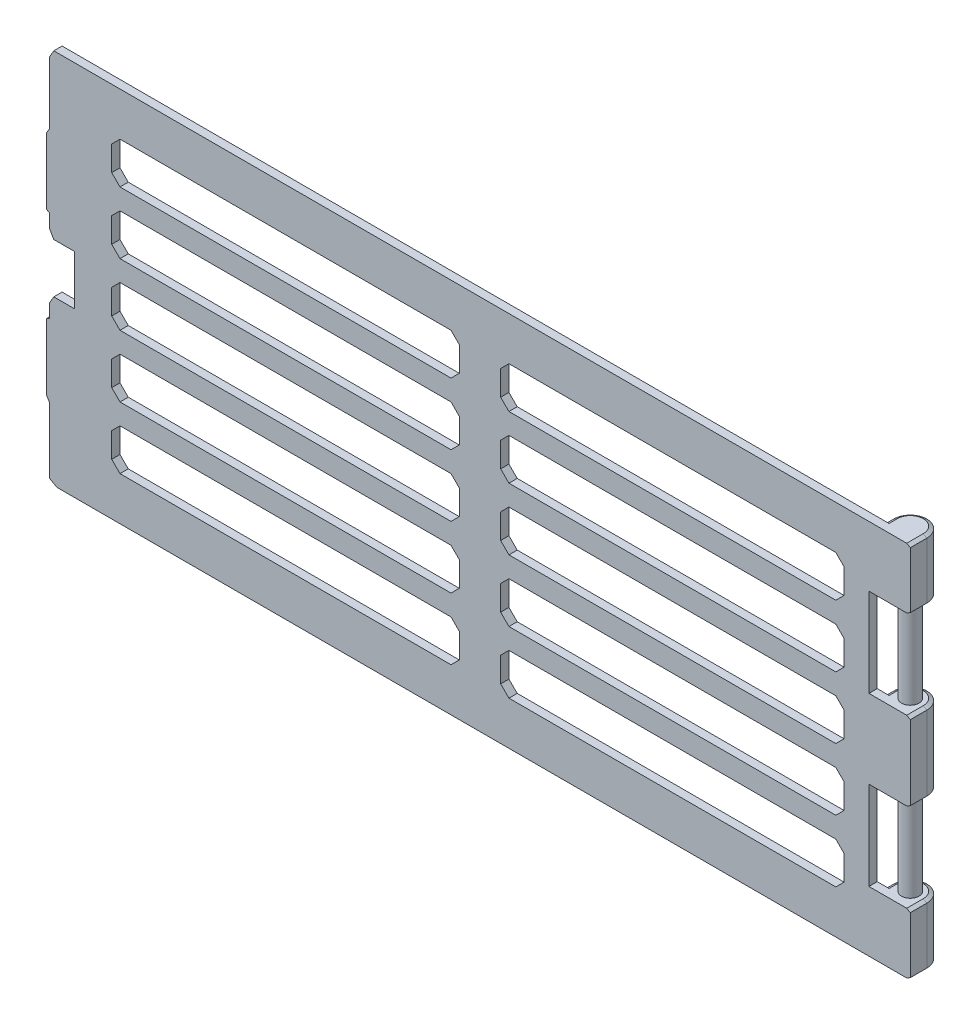
SolidWorks part; units mm, degrees
ref_plane "前视基准面" through (0, 0, 0) normal (0, 0, 1) x (1, 0, 0)
ref_plane "上视基准面" through (0, 0, 0) normal (0, 1, 0) x (1, 0, 0)
ref_plane "右视基准面" through (0, 0, 0) normal (1, 0, 0) x (0, 0, -1)
other "Configuration Table"
sketch "草图1" plane through (0, 0, 0) normal (0, 0, 1) x (1, 0, 0)
  line L1 (-104, 45.5) -> (104, 45.5)
  line L2 (-104, 45.5) -> (-104, -45.5)
  line L3 (-104, -45.5) -> (104, -45.5)
  line L4 (104, 45.5) -> (104, -45.5)
  line L5 (0, -45.5) -> (0, 45.5) construction
  line L6 (-104, 0) -> (104, 0) construction
  point P0 (0, 0)
  dimension "D1" = 91
  dimension "D2" = 208
extrude "凸台-拉伸1" add sketch "草图1" along normal blind 2
sketch "草图3" plane through (0, 45.5, 0) normal (0, 1, 0) x (1, 0, 0)
  line L1 (96, -2) -> (104, -2)
  line L2 (96, -2) -> (96, 6)
  line L3 (96, 6) -> (104, 6)
  line L4 (104, -2) -> (104, 6)
  line L5 (100, 6) -> (100, -2) construction
  line L6 (96, 2) -> (104, 2) construction
  line L7 (104, -2) -> (104, 0) construction
  line L8 (104, -2) -> (-104, -2) construction
  point P0 (100, 2)
  dimension "D1" = 8
  dimension "D2" = 8
extrude "凸台-拉伸2" add sketch "草图3" along direction (0, 1, 0) on the side against the normal up to surface (91 mm away) up to face at (0, -45.5, 1)
sketch "草图2" plane through (0, 0, 2) normal (0, 0, 1) x (1, 0, 0)
  line L0 (104, 30.9) -> (94, 30.9)
  line L1 (104, -45.5) -> (104, 45.5) construction
  line L2 (94, 30.9) -> (94, 45.5)
  line L3 (104, 45.5) -> (-104, 45.5) construction
  line L4 (104, -30.9) -> (94, -30.9)
  line L5 (94, -30.9) -> (94, -45.5)
  line L6 (-104, -45.5) -> (104, -45.5) construction
  line L7 (104, 9.5) -> (94, 9.5)
  line L8 (94, 9.5) -> (94, -9.5)
  line L9 (94, -9.5) -> (104, -9.5)
  line L10 (104, 9.5) -> (104, -9.5)
  line L11 (104, -30.9) -> (104, -45.5)
  line L12 (104, -45.5) -> (94, -45.5)
  line L13 (104, 30.9) -> (104, 45.5)
  line L14 (104, 45.5) -> (94, 45.5)
  line L15 (94, 30.9) -> (94, 9.5)
  line L16 (104, 30.9) -> (104, 9.5)
  line L17 (104, -9.5) -> (104, -30.9)
  line L18 (94, -9.5) -> (94, -30.9)
  point P14 (104, 0)
  dimension "D1" = 9.5
  dimension "D2" = 19
  dimension "D3" = 21.4
  dimension "D4" = 21.4
  dimension "D5" = 10
extrude "切除-拉伸1" cut sketch "草图2" against normal mid plane 46
sketch "草图4" plane through (0, 45.5, 0) normal (0, 1, 0) x (1, 0, 0)
  line L0 (104, 6) -> (96, -2) construction
  line L1 (104, -2) -> (-104, -2) construction
  line L2 (96, 6) -> (96, 0) construction
  circle A0 centre (100, 2) radius 2.1
  dimension "D1" = 4.2
extrude "凸台-拉伸3" add sketch "草图4" against normal up to surface (91 mm away) up to face at (32, -45.5, -1.3333)
fillet "圆角1" radius 4 6 edges at (96, 38.2, -6) (96, 0, -6) (96, -38.2, -6) (104, -38.2, -6) (104, 0, -6) (104, 38.2, -6)
sketch "草图6" plane through (0, 0, 2) normal (0, 0, 1) x (1, 0, 0)
  line L0 (88, -45.5) -> (88, 45.5)
  line L1 (-104, -45.5) -> (104, -45.5) construction
  line L2 (104, 45.5) -> (-104, 45.5) construction
  line L3 (104, 30.9) -> (104, 45.5) construction
  line L4 (-89, -45.5) -> (-89, 45.5)
  line L5 (-104, 45.5) -> (-104, -45.5) construction
  line L6 (-89, 0) -> (88, 0)
  line L7 (88, 15) -> (-89, 15)
  line L8 (88, 30) -> (-89, 30)
  dimension "D1" = 16
  dimension "D2" = 15
  dimension "D3" = 15
  dimension "D4" = 15
extrude "切除-拉伸-薄壁1" cut sketch "草图6" against normal through all thin contours L8 | L7 | L6 thin type mid plane wall 10
mirror "镜向1" about plane through (0, 0, 0) normal (0, 1, 0) of "切除-拉伸-薄壁1"
sketch "草图7" plane through (0, 0, 2) normal (0, 0, 1) x (1, 0, 0)
  line L0 (104, 45.5) -> (-104, 45.5) construction
  line L1 (-5, -45.5) -> (5, -45.5)
  line L2 (-5, -45.5) -> (-5, 45.5)
  line L3 (-5, 45.5) -> (5, 45.5)
  line L4 (5, -45.5) -> (5, 45.5)
  line L5 (0, 45.5) -> (0, -45.5) construction
  line L6 (-5, 0) -> (5, 0) construction
  point P0 (0, 0)
  dimension "D1" = 10
extrude "凸台-拉伸4" add sketch "草图7" against normal up to surface (2 mm away) up to face at (-0.5, -15, 0)
chamfer "倒角1" distance 2 angle 45 40 edges at (88, 10, 1) (88, 25, 1) (88, 35, 1) (88, 20, 1) (88, 5, 1) (5, 25, 1) (5, 10, 1) (5, 5, 1) (5, 20, 1) (5, 35, 1) (-5, 5, 1) (-5, 10, 1) (-5, 20, 1) (-5, 25, 1) (-5, 35, 1) (-89, 5, 1) (-89, 10, 1) (-89, 20, 1) (-89, 25, 1) (-89, 35, 1) (-5, -35, 1) (-5, -20, 1) (-5, -5, 1) (-5, -10, 1) (-5, -25, 1) (-89, -25, 1) (-89, -10, 1) (-89, -35, 1) (-89, -20, 1) (-89, -5, 1) (5, -35, 1) (5, -20, 1) (5, -5, 1) (5, -25, 1) (5, -10, 1) (88, -25, 1) (88, -10, 1) (88, -5, 1) (88, -20, 1) (88, -35, 1)
sketch "草图5" plane through (0, 45.5, 0) normal (0, 1, 0) x (1, 0, 0)
  line L1 (-104, -20) -> (84, -20)
  line L2 (-104, -20) -> (-104, 0)
  line L3 (-104, 0) -> (84, 0)
  line L4 (84, -20) -> (84, 0)
  line L5 (-10, 0) -> (-10, -20) construction
  line L6 (-104, -10) -> (84, -10) construction
  line L7 (-55, 0) -> (55, 0) construction
  line L8 (-104, -2) -> (-104, 0) construction
  line L9 (104, -2) -> (104, 2) construction
  point P0 (-10, -10)
  dimension "D1" = 20
  dimension "D2" = 20
extrude "切除-拉伸2" [suppressed] cut sketch "草图5" against normal through all
sketch "草图8" plane through (0, 0, 2) normal (0, 0, 1) x (1, 0, 0)
  line L0 (55, 0) -> (-55, 0) construction
  line L1 (-110, -6) -> (-98, -6)
  line L2 (-110, -6) -> (-110, 6)
  line L3 (-110, 6) -> (-98, 6)
  line L4 (-98, -6) -> (-98, 6)
  line L5 (-104, 6) -> (-104, -6) construction
  line L6 (-110, 0) -> (-98, 0) construction
  line L7 (-104, 45.5) -> (-104, -45.5) construction
  point P0 (-104, 0)
  dimension "D1" = 12
  dimension "D2" = 12
extrude "切除-拉伸3" cut sketch "草图8" against normal blind 10
sketch "草图9" plane through (0, 0, 0) normal (0, 1, 0) x (1, 0, 0)
  line L0 (-104, -2) -> (-102, -2)
  line L1 (104, -2) -> (-104, -2) construction
  line L2 (-102, -2) -> (-102, 4.5)
  line L3 (-102, 4.5) -> (-104, 4.5)
  line L4 (-104, 4.5) -> (-104, -2)
  line L5 (-102, 3) -> (-102.8, 2.2)
  line L6 (-102.8, 2.2) -> (-102, 1.4)
  line L7 (-102.8, 2.2) -> (-102, 2.2)
  line L8 (-102, 3.2121) -> (-103.0121, 2.2)
  line L9 (-103.0121, 2.2) -> (-102, 1.1879)
  line L10 (-104, 3.2121) -> (-104.8, 2.2)
  line L11 (-104.8, 2.2) -> (-104, 1.1879)
  line L12 (-104, 3.2121) -> (-102, 3.2121) construction
  line L13 (-104, 1.1879) -> (-102, 1.1879) construction
  line L14 (-104.8, 2.2) -> (-103.0121, 2.2) construction
  line L15 (-104, -2) -> (-104.8, -2)
  line L16 (-104.8, -2) -> (-104.8, 2.2)
  dimension "D1" = 2
  dimension "D2" = 6.5
  dimension "D3" = 0.8
  dimension "D4" = 4.2
  dimension "D5" = 0.15
  dimension "D6" = 0.15
  dimension "D7" = 0.8
  dimension "D8" = 1.0121
  dimension "D9" = 0.8
extrude "凸台-拉伸5" add sketch "草图9" along normal blind 15 from offset 12 contours L9 L8 L2 L3 L4 L0 | L10 L11 L4 | L16 L15 L4 L11
fillet "圆角2" radius 1.5 2 edges at (-104, 19.5, -3.2121) (-104.8, 19.5, -2.2)
mirror "镜向2" about plane through (0, 0, 0) normal (0, 1, 0) of "圆角2", "凸台-拉伸5"
chamfer "倒角2" distance 1 angle 60 8 edges at (-104, -27, 1) (-104, -12, 1) (-104, 12, 1) (-104, 27, 1) (-104, -45.5, 1) (-104, 45.5, 1) (-104, 6, 1) (-104, -6, 1) first distance on face at (-103.4932, -27, -1.7249) first distance on face at (-104, -9, 1) first distance on face at (-104, 9, 1) first distance on face at (-103.4932, 27, -1.7249) first distance on face at (-104, -36.25, 1) first distance on face at (41.7143, 45.5, -1.0938) first distance on face at (-101, 6, 1) first distance on face at (-101, -6, 1)
chamfer "倒角3" distance 0.5 angle 60 24 edges at (104, 45.5, 0) (102.8284, 45.5, -4.8284) (96, 45.5, -1) (97.1716, 45.5, -4.8284) (104, 30.9, 0) (96, 30.9, -1) (102.8284, 30.9, -4.8284) (97.1716, 30.9, -4.8284) (104, 9.5, 0) (102.8284, 9.5, -4.8284) (96, 9.5, -1) (97.1716, 9.5, -4.8284) (104, -9.5, 0) (96, -9.5, -1) (102.8284, -9.5, -4.8284) (97.1716, -9.5, -4.8284) (104, -30.9, 0) (102.8284, -30.9, -4.8284) (96, -30.9, -1) (97.1716, -30.9, -4.8284) (104, -45.5, 0) (96, -45.5, -1) (102.8284, -45.5, -4.8284) (97.1716, -45.5, -4.8284) first distance on face at (104, 38.2, 0) first distance on face at (102.4142, 38.2, -4.4142) first distance on face at (96, 38.2, -1) first distance on face at (97.5858, 38.2, -4.4142) first distance on face at (104, 0, 0) first distance on face at (102.4142, 0, -4.4142) first distance on face at (96, 0, -1) first distance on face at (97.5858, 0, -4.4142) first distance on face at (104, -38.2, 0) first distance on face at (102.4142, -38.2, -4.4142) first distance on face at (96, -38.2, -1) first distance on face at (97.5858, -38.2, -4.4142)
